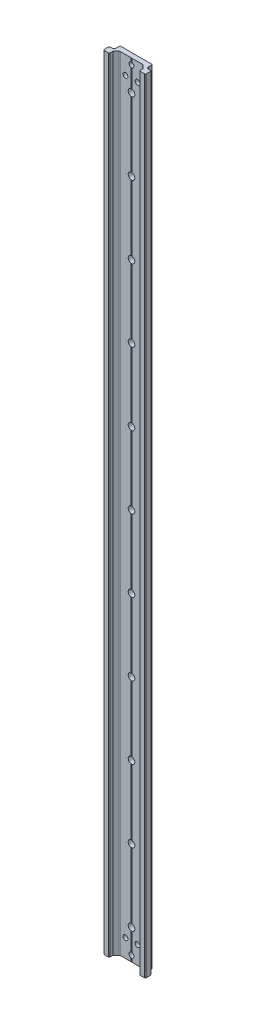
SolidWorks part; units mm, degrees
ref_plane "Plan de face" through (0, 0, 0) normal (0, 0, 1) x (1, 0, 0)
ref_plane "Plan de dessus" through (0, 0, 0) normal (0, 1, 0) x (1, 0, 0)
ref_plane "Plan de droite" through (0, 0, 0) normal (1, 0, 0) x (0, 0, -1)
ref_plane "Plan1" through (0, 325, 0) normal (0, 1, 0) x (1, 0, 0)
sketch "Esquisse1" plane through (0, 325, 0) normal (0, 1, 0) x (1, 0, 0)
  line L0 (-9.7, 1) -> (9.7, 1)
  line L1 (9.7, 1) -> (12.5, -1.8)
  line L2 (12.5, -1.8) -> (12.5, -5)
  line L3 (12.5, -5) -> (17.5, -5)
  line L4 (17.5, -5) -> (17.5, 5)
  line L5 (17.5, 5) -> (-17.5, 5)
  line L6 (-17.5, 5) -> (-17.5, -5)
  line L7 (-17.5, -5) -> (-12.5, -5)
  line L8 (-12.5, -5) -> (-12.5, -1.8)
  line L9 (-12.5, -1.8) -> (-9.7, 1)
extrude "Boss.-Extru.1" add sketch "Esquisse1" against normal blind 650
sketch "Esquisse2" plane through (0, -325, 0) normal (0, -1, 0) x (1, 0, 0)
  line L0 (-14.3, 0) -> (-17.5, 0)
  line L1 (-17.5, 0) -> (-17.5, -5)
  line L2 (-17.5, -5) -> (-13.5, -5)
  line L3 (-13.5, -5) -> (-13.5, -0.8)
  line L4 (-13.5, -0.8) -> (-14.3, 0)
extrude "Enlèv. mat.-Extru.1" cut sketch "Esquisse2" against normal through all
sketch "Esquisse3" plane through (0, -325, 0) normal (0, -1, 0) x (1, 0, 0)
  line L0 (0.25, -1) -> (-0.25, -1)
  line L1 (-0.25, -1) -> (0, -1.1443)
  line L2 (0, -1.1443) -> (0.25, -1)
extrude "Enlèv. mat.-Extru.2" cut sketch "Esquisse3" against normal blind 650
sketch "Esquisse4" plane through (0, -325, 0) normal (0, -1, 0) x (1, 0, 0)
  line L0 (13.5, -0.8) -> (13.5, -5)
  line L1 (13.5, -5) -> (17.5, -5)
  line L2 (17.5, -5) -> (17.5, 0)
  line L3 (17.5, 0) -> (14.3, 0)
  line L4 (14.3, 0) -> (13.5, -0.8)
extrude "Enlèv. mat.-Extru.3" cut sketch "Esquisse4" against normal through all
sketch "Esquisse5" plane through (0, -325, 0) normal (0, -1, 0) x (1, 0, 0)
  line L0 (-7.5, -5) -> (7.5, -5)
  line L1 (7.5, -5) -> (7.4, -4.9)
  line L2 (7.4, -4.9) -> (-7.4, -4.9)
  line L3 (-7.4, -4.9) -> (-7.5, -5)
extrude "Enlèv. mat.-Extru.4" cut sketch "Esquisse5" against normal blind 650
hole_wizard "Diamètre du perçage Ø5.5 (5.5)1" positions "Esquisse7" profile "Esquisse6" hole size "Ø5.5" standard "Ansi Metric"
sketch "Esquisse7" plane through (0, 0, -4.9) normal (0, 0, -1) x (-1, 0, 0)
  point P0 (0, 300)
  point P1 (0, 240)
  point P2 (0, 180)
  point P3 (0, 120)
  point P4 (0, 60)
  point P5 (0, 0)
  point P6 (0, -60)
  point P7 (0, -120)
  point P8 (0, -180)
  point P9 (0, -240)
  point P10 (0, -300)
sketch "Esquisse6" plane through (0, 300, -4.9) normal (1, 0, 0) x (0, 1, 0)
  line L0 (0, 0) -> (0, 9.9)
  line L1 (0, 9.9) -> (2.75, 9.9)
  line L2 (2.75, 9.9) -> (2.75, 0)
  line L5 (2.75, 0) -> (0, 0)
  line L11 (0, -6.35) -> (0, 107.95) construction
  dimension "Diamètre du perçage jusqu'au prochain" = 5.5
  dimension "Profondeur du perçage jusqu'au prochain" = 9.9
chamfer "Chanfrein1" distance 0.5 angle 45 2 edges at (17.5, 0, 5) (-17.5, 0, 5) first distance on face at (17.5, 0, 2.5) first distance on face at (-15, 0, 5)
chamfer "Chanfrein2" distance 0.3 angle 45 2 edges at (-13.5, 0, -5) (13.5, 0, -5)
chamfer "Chanfrein3" distance 0.5 angle 45 3 edges at (12.5, 0, 5) (-17.5, 0, 0) (-12.5, 0, 5) first distance on face at (14.75, 0, 5) first distance on face at (-15.9, 0, 0) first distance on face at (-12.5, 0, 3.4)
chamfer "Chanfrein4" distance 0.5 angle 45 1 edges at (17.5, 0, 0) first distance on face at (15.9, 0, 0)
fillet "Congé1" radius 1.5 2 edges at (9.7, 0, -1) (-9.7, 0, -1) tangent propagation no
fillet "Congé2" radius 2 2 edges at (13.5, 0, -0.8) (-13.5, 0, -0.8) tangent propagation no
sketch "Esquisse8" plane through (0, 0, -1) normal (0, 0, 1) x (1, 0, 0)
  line L0 (-9.0787, -325) -> (-0.25, -325) construction
  line L1 (0.25, -325) -> (9.0787, -325) construction
  line L2 (-9.0787, 325) -> (-0.25, 325) construction
  line L3 (0.25, 325) -> (9.0787, 325) construction
  line L4 (0, 325) -> (0, 302.75) construction
  circle A0 centre (-5, -310) radius 2
  circle A1 centre (5, -310) radius 2
  circle A2 centre (-5, 310) radius 2
  circle A3 centre (5, 310) radius 2
  circle A4 centre (0, -320) radius 2.0932
  circle A5 centre (0, 320) radius 2
  dimension "D1" = 4
  dimension "D2" = 4
  dimension "D3" = 4
  dimension "D4" = 4
  dimension "D13" = 4.1865
  dimension "D15" = 4
  dimension "D5" = 15
  dimension "D6" = 15
  dimension "D7" = 15
  dimension "D8" = 15
  dimension "D9" = 5
  dimension "D10" = 5
  dimension "D11" = 5
  dimension "D12" = 5
  dimension "D14" = 5
  dimension "D16" = 5
extrude "Enlèv. mat.-Extru.5" cut sketch "Esquisse8" against normal blind 10
